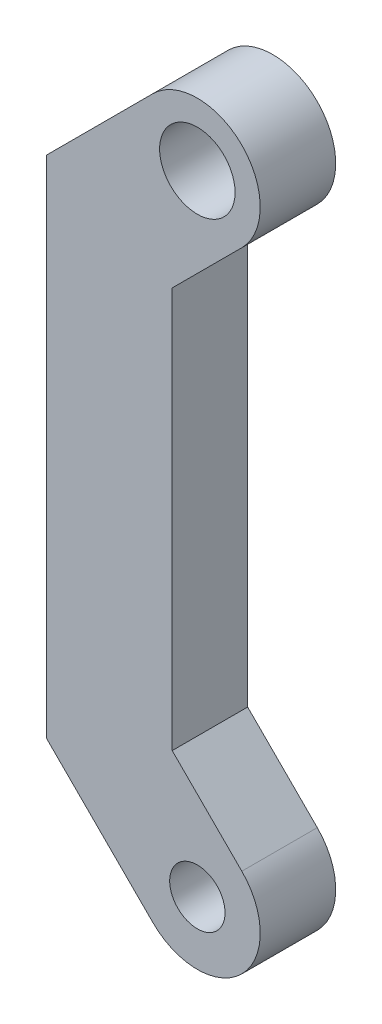
SolidWorks part; units mm, degrees
ref_plane "Alzado" through (0, 0, 0) normal (0, 0, 1) x (1, 0, 0)
ref_plane "Planta" through (0, 0, 0) normal (0, 1, 0) x (1, 0, 0)
ref_plane "Vista lateral" through (0, 0, 0) normal (1, 0, 0) x (0, 0, -1)
sketch "Croquis1" plane through (0, 0, 0) normal (0, 0, 1) x (1, 0, 0)
  line L0 (0, 0) -> (0, 25) construction
  line L1 (0, 0) -> (-3.5, 3.5) construction
  line L2 (-3.5, 3.5) -> (-3.5, 21.5) construction
  line L3 (-3.5, 21.5) -> (0, 25) construction
  line L4 (1.7678, 1.7678) -> (-1, 4.5355)
  line L5 (-1, 4.5355) -> (-1, 20.4645)
  line L6 (-1, 20.4645) -> (1.7678, 23.2322)
  line L7 (-1.7678, -1.7678) -> (-6, 2.4645)
  line L8 (-6, 2.4645) -> (-6, 22.5355)
  line L9 (-6, 22.5355) -> (-1.7678, 26.7678)
  circle A0 centre (0, 0) radius 1.1
  circle A1 centre (0, 0) radius 2.5
  circle A4 centre (0, 25) radius 1.5
  circle A5 centre (0, 25) radius 2.5
  dimension "D1" = 2.2
  dimension "D2" = 5
  dimension "D3" = 3
  dimension "D4" = 5
  dimension "D5" = 25
  dimension "D6" = 45
  dimension "D7" = 45
  dimension "D8" = 18
  dimension "D9" = 2.5
  dimension "D10" = 2.5
extrude "Saliente-Extruir1" add sketch "Croquis1" along normal blind 3 contours A5 L9 L8 L7 A1 L4 L5 L6 | A5 A4 | A1 A0 region at (-3.3612, 12.5, 0) region at (2.2444, 0.9296, 0) region at (-1.7178, 23.2822, 0)
